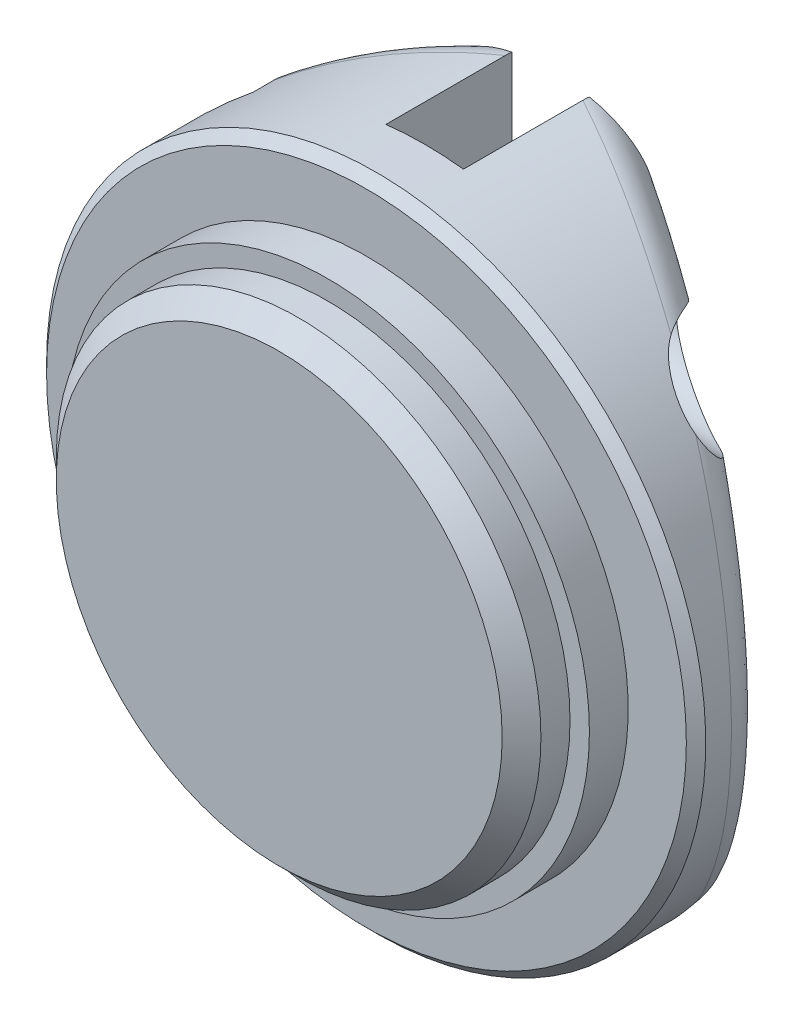
SolidWorks part; units mm, degrees
ref_plane "Front Plane" through (0, 0, 0) normal (0, 0, 1) x (1, 0, 0)
ref_plane "Top Plane" through (0, 0, 0) normal (0, 1, 0) x (1, 0, 0)
ref_plane "Right Plane" through (0, 0, 0) normal (1, 0, 0) x (0, 0, -1)
sketch "Sketch1" plane through (0, 0, 0) normal (0, 0, 1) x (1, 0, 0)
  circle A0 centre (0, 0) radius 12.5
  dimension "D1" = 25
extrude "Boss-Extrude1" add sketch "Sketch1" along normal blind 4.5
sketch "Sketch2" plane through (0, 0, 0) normal (0, 0, -1) x (-1, 0, 0)
  circle A0 centre (0, 0) radius 17
  dimension "D1" = 34
extrude "Boss-Extrude2" add sketch "Sketch2" along normal blind 3
chamfer "Chamfer1" distance 1 angle 45 1 edges at (12.5, 0, 4.5)
sketch "Sketch3" plane through (0, 0, 0) normal (0, 1, 0) x (1, 0, 0)
  line L0 (0, 0) -> (0, 9.5) construction
  line L1 (-17, 3) -> (-5.274, 9.5)
  line L2 (-5.274, 9.5) -> (-2, 9.5)
  line L3 (-2, 9.5) -> (-2, 3)
  line L4 (17, 3) -> (-17, 3) construction
  line L5 (-17, 3) -> (-2, 3)
  line L6 (17, 3) -> (2, 3)
  line L7 (2, 9.5) -> (2, 3)
  line L8 (5.274, 9.5) -> (2, 9.5)
  line L9 (17, 3) -> (5.274, 9.5)
  dimension "D1" = 4
  dimension "D2" = 6.5
extrude "Boss-Extrude3" add sketch "Sketch3" along normal mid plane 40
sketch "Sketch4" plane through (0, 0, 0) normal (1, 0, 0) x (0, 0, -1)
  line L0 (5.75, 11) -> (5.75, -11) construction
  line L1 (9.5, 20) -> (9.5, -20) construction
  circle A0 centre (5.75, 11) radius 1.25
  circle A1 centre (5.75, -11) radius 1.25
  point P4 (5.75, 0)
  dimension "D1" = 2.5
  dimension "D2" = 22
  dimension "D3" = 3.75
extrude "Cut-Extrude1" cut sketch "Sketch4" against normal through all both and the other way through all
sketch "Sketch5" plane through (0, 0, 0) normal (0, 0, 1) x (1, 0, 0)
  circle A0 centre (0, 0) radius 13.5
  dimension "D1" = 27
extrude "Boss-Extrude4" add sketch "Sketch5" along normal blind 2
sketch "Sketch6" plane through (0, 0, 4.5) normal (0, 0, 1) x (1, 0, 0)
  line L1 (23.3622, -22.945) -> (-23.3622, -22.945)
  line L2 (23.3622, -22.945) -> (23.3622, 22.945)
  line L3 (23.3622, 22.945) -> (-23.3622, 22.945)
  line L4 (-23.3622, -22.945) -> (-23.3622, 22.945)
  line L5 (23.3622, -22.945) -> (-23.3622, 22.945) construction
  line L6 (23.3622, 22.945) -> (-23.3622, -22.945) construction
  circle A0 centre (0, 0) radius 17
  arc A1 (2, -16.8819) -> (17, 0) centre (0, 0) ccw construction
extrude "Cut-Extrude2" cut sketch "Sketch6" against normal through all both and the other way through all
sketch "Sketch7" plane through (0, 0, -3) normal (0, 0, -1) x (-1, 0, 0)
  line L0 (2, 16.8819) -> (2, -16.8819) construction
  line L1 (-2, 7) -> (2, 7)
  line L2 (-2, 7) -> (-2, -7)
  line L3 (-2, -7) -> (2, -7)
  line L4 (2, 7) -> (2, -7)
  line L5 (-2, 7) -> (2, -7) construction
  line L6 (-2, -7) -> (2, 7) construction
  point P0 (0, 0)
  dimension "D1" = 14
extrude "Cut-Extrude3" cut sketch "Sketch7" against normal blind 3
sketch "Sketch8" plane through (0, 0, 0) normal (1, 0, 0) x (0, 0, -1)
  circle A0 centre (5.75, 11) radius 2.25
  circle A1 centre (5.75, -11) radius 2.25
  dimension "D1" = 4.5
extrude "Cut-Extrude4" cut sketch "Sketch8" along normal blind 33 from offset 6
sketch "Sketch9" plane through (0, 0, 0) normal (1, 0, 0) x (0, 0, -1)
  line L1 (7.3377, 8.25) -> (8.9254, 11)
  line L2 (8.9254, 11) -> (7.3377, 13.75)
  line L3 (7.3377, 13.75) -> (4.1623, 13.75)
  line L4 (4.1623, 13.75) -> (2.5746, 11)
  line L5 (2.5746, 11) -> (4.1623, 8.25)
  line L6 (4.1623, 8.25) -> (7.3377, 8.25)
  line L7 (4.1623, -13.75) -> (7.3377, -13.75)
  line L8 (7.3377, -13.75) -> (8.9254, -11)
  line L9 (8.9254, -11) -> (7.3377, -8.25)
  line L10 (7.3377, -8.25) -> (4.1623, -8.25)
  line L11 (4.1623, -8.25) -> (2.5746, -11)
  line L12 (2.5746, -11) -> (4.1623, -13.75)
  circle A0 centre (5.75, 11) radius 2.75 construction
  circle A1 centre (5.75, -11) radius 2.75 construction
  dimension "D1" = 5.5
extrude "Cut-Extrude5" cut sketch "Sketch9" against normal blind 33 from offset 5 offset against normal yes
fillet "Fillet1" radius 2 6 edges at (8.1708, 14.9076, -7.8942) (17, 0, -3) (8.1708, -14.9076, -7.8942) (-7.73, -15.1409, -8.1386) (-7.73, 15.1409, -8.1386) (-17, 0, -3)
chamfer "Chamfer2" distance 0.5 angle 45 1 edges at (-17, 0, 0)
